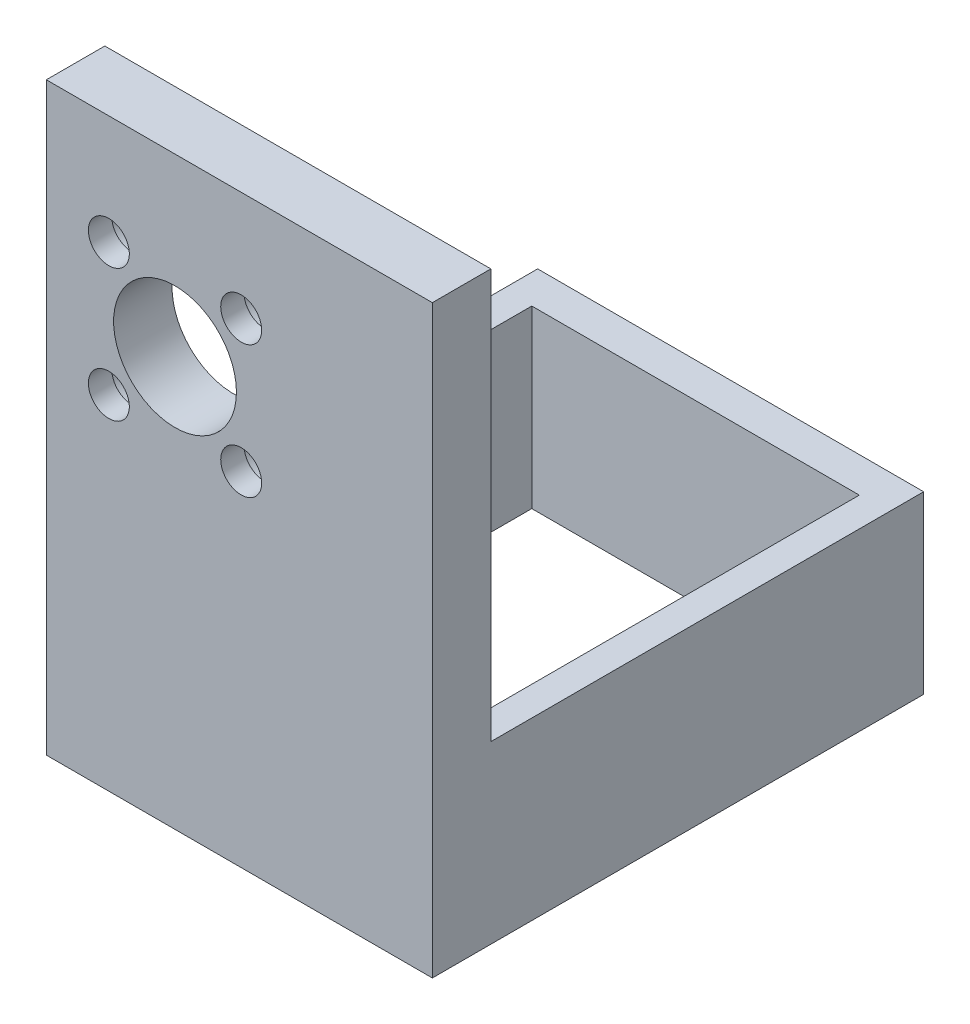
SolidWorks part; units mm, degrees
ref_plane "Płaszczyzna przednia" through (0, 0, 0) normal (0, 0, 1) x (1, 0, 0)
ref_plane "Płaszczyzna górna" through (0, 0, 0) normal (0, 1, 0) x (1, 0, 0)
ref_plane "Płaszczyzna prawa" through (0, 0, 0) normal (1, 0, 0) x (0, 0, -1)
sketch "Szkic1" plane through (0, 0, 0) normal (0, 0, 1) x (1, 0, 0)
  line L1 (-16.5, -7.5) -> (16.5, -7.5)
  line L2 (-16.5, -7.5) -> (-16.5, 7.5)
  line L3 (-16.5, 7.5) -> (16.5, 7.5)
  line L4 (16.5, -7.5) -> (16.5, 7.5)
  line L5 (-16.5, -7.5) -> (16.5, 7.5) construction
  line L6 (-16.5, 7.5) -> (16.5, -7.5) construction
  point P0 (0, 0)
  dimension "D1" = 15
  dimension "D2" = 33
extrude "Dodanie-wyciągnięcie1" add sketch "Szkic1" along normal blind 40
sketch "Szkic2" plane through (0, 7.5, 0) normal (0, 1, 0) x (1, 0, 0)
  line L0 (16.5, 0) -> (16.5, -40)
  line L1 (16.5, 0) -> (16.5, -40)
  line L2 (16.5, -40) -> (-16.5, -40)
  line L3 (16.5, -40) -> (-16.5, -40)
  line L4 (-16.5, -40) -> (-16.5, 0)
  line L5 (-16.5, -40) -> (-16.5, 0)
  line L6 (-16.5, 0) -> (16.5, 0)
  line L7 (-16.5, 0) -> (16.5, 0)
  line L8 (-16.5, -20) -> (16.5, -20)
  line L10 (-14, -37) -> (14, -37)
  line L11 (-14, -37) -> (-14, -3)
  line L12 (-14, -3) -> (14, -3)
  line L13 (14, -37) -> (14, -3)
  line L14 (-14, -37) -> (14, -3) construction
  line L15 (-14, -3) -> (14, -37) construction
  point P6 (0, -20)
  dimension "D1" = 28
  dimension "D2" = 34
extrude "Wytnij-wyciągnięcie1" cut sketch "Szkic2" against normal blind 29 contours L12 L13 L10 L11
sketch "Szkic3" plane through (0, 0, 40) normal (0, 0, 1) x (1, 0, 0)
  line L0 (-16.5, -7.5) -> (16.5, -7.5) construction
  line L1 (-16.5, -7.5) -> (16.5, -7.5)
  line L2 (-16.5, -7.5) -> (-16.5, 42.5)
  line L3 (-16.5, 42.5) -> (16.5, 42.5)
  line L4 (16.5, -7.5) -> (16.5, 42.5)
  line L5 (-16.5, 7.5) -> (-16.5, -7.5) construction
  line L6 (-16.5, 7.5) -> (16.5, 7.5)
  line L7 (16.5, 7.5) -> (-16.5, 7.5) construction
  line L8 (16.5, 7.5) -> (0, 7.5)
  line L9 (0, 42.5) -> (0, 7.5)
  line L10 (-5.5, 27.5) -> (5.5, 27.5)
  circle A0 centre (-5.5, 27.5) radius 4
  circle A1 centre (-5.5, 27.5) radius 11
  circle A2 centre (-5.5, 27.5) radius 8
  circle A3 centre (0.1569, 33.1569) radius 1.75
  circle A4 centre (0.1569, 21.8431) radius 1.75
  circle A5 centre (-11.1569, 21.8431) radius 1.75
  circle A6 centre (-11.1569, 33.1569) radius 1.75
  point P31 (-5.5, 27.5)
  dimension "D1" = 8
  dimension "D2" = 22
  dimension "D3" = 16
  dimension "D4" = 3.5
  dimension "D7" = 15
  dimension "D6" = 35
  dimension "D8" = 5.5
  dimension "D5" = 4
extrude "Dodanie-wyciągnięcie2" add sketch "Szkic3" along normal blind 2 contours L3 L4 L1 L2
extrude "Wytnij-wyciągnięcie2" cut sketch "Szkic3<3>" along normal blind 16 contours A0
sketch "Szkic3<3>" plane through (0, 0, 40) normal (0, 0, 1) x (1, 0, 0) same geometry as "Szkic3"
sketch "Szkic7" plane through (0, 0, 40) normal (0, 0, -1) x (-1, 0, 0)
  line L0 (16.5, -7.5) -> (-16.5, -7.5)
  line L1 (16.5, -7.5) -> (-16.5, -7.5)
  line L2 (-16.5, -7.5) -> (-16.5, 42.5)
  line L3 (-16.5, -7.5) -> (-16.5, 42.5)
  line L4 (-16.5, 42.5) -> (16.5, 42.5)
  line L5 (-16.5, 42.5) -> (16.5, 42.5)
  line L6 (16.5, 42.5) -> (16.5, -7.5)
  line L7 (16.5, 42.5) -> (16.5, -7.5)
extrude "Dodanie-wyciągnięcie3" add sketch "Szkic7" along normal blind 3
extrude "Wytnij-wyciągnięcie5" cut sketch "Szkic3<5>" along normal mid plane 29 contours A6
sketch "Szkic3<5>" plane through (0, 0, 40) normal (0, 0, 1) x (1, 0, 0) same geometry as "Szkic3"
extrude "Wytnij-wyciągnięcie6" cut sketch "Szkic3<6>" along normal mid plane 29 contours A5
sketch "Szkic3<6>" plane through (0, 0, 40) normal (0, 0, 1) x (1, 0, 0) same geometry as "Szkic3"
extrude "Wytnij-wyciągnięcie7" cut sketch "Szkic3<7>" along normal mid plane 17 contours A3
sketch "Szkic3<7>" plane through (0, 0, 40) normal (0, 0, 1) x (1, 0, 0) same geometry as "Szkic3"
sketch "Szkic5" plane through (0, 0, 42) normal (0, 0, 1) x (1, 0, 0)
  circle A0 centre (-5.5, 27.5) radius 5.25
  dimension "D1" = 10.5
extrude "Wytnij-wyciągnięcie10" cut sketch "Szkic5" against normal blind 36
extrude "Wytnij-wyciągnięcie8" cut sketch "Szkic3<8>" along normal mid plane 11 contours A4
sketch "Szkic3<8>" plane through (0, 0, 40) normal (0, 0, 1) x (1, 0, 0) same geometry as "Szkic3"
sketch "Szkic9" plane through (0, 0, 37) normal (0, 0, -1) x (-1, 0, 0)
  circle A0 centre (11.1569, 33.1569) radius 2.5
  circle A1 centre (11.1569, 21.8431) radius 2.5
  circle A2 centre (-0.1569, 21.8431) radius 2.5
  circle A3 centre (-0.1569, 33.1569) radius 2.5
  dimension "D1" = 5
  dimension "D2" = 5
  dimension "D3" = 5
  dimension "D4" = 5
extrude "Wytnij-wyciągnięcie11" cut sketch "Szkic9" against normal blind 3 contours A3
extrude "Wytnij-wyciągnięcie12" cut sketch "Szkic9<4>" against normal blind 3 contours A0
sketch "Szkic9<4>" plane through (0, 0, 37) normal (0, 0, -1) x (-1, 0, 0) same geometry as "Szkic9"
extrude "Wytnij-wyciągnięcie13" cut sketch "Szkic9<5>" against normal blind 3 contours A1
sketch "Szkic9<5>" plane through (0, 0, 37) normal (0, 0, -1) x (-1, 0, 0) same geometry as "Szkic9"
extrude "Wytnij-wyciągnięcie14" cut sketch "Szkic9<6>" against normal blind 3 contours A2
sketch "Szkic9<6>" plane through (0, 0, 37) normal (0, 0, -1) x (-1, 0, 0) same geometry as "Szkic9"
